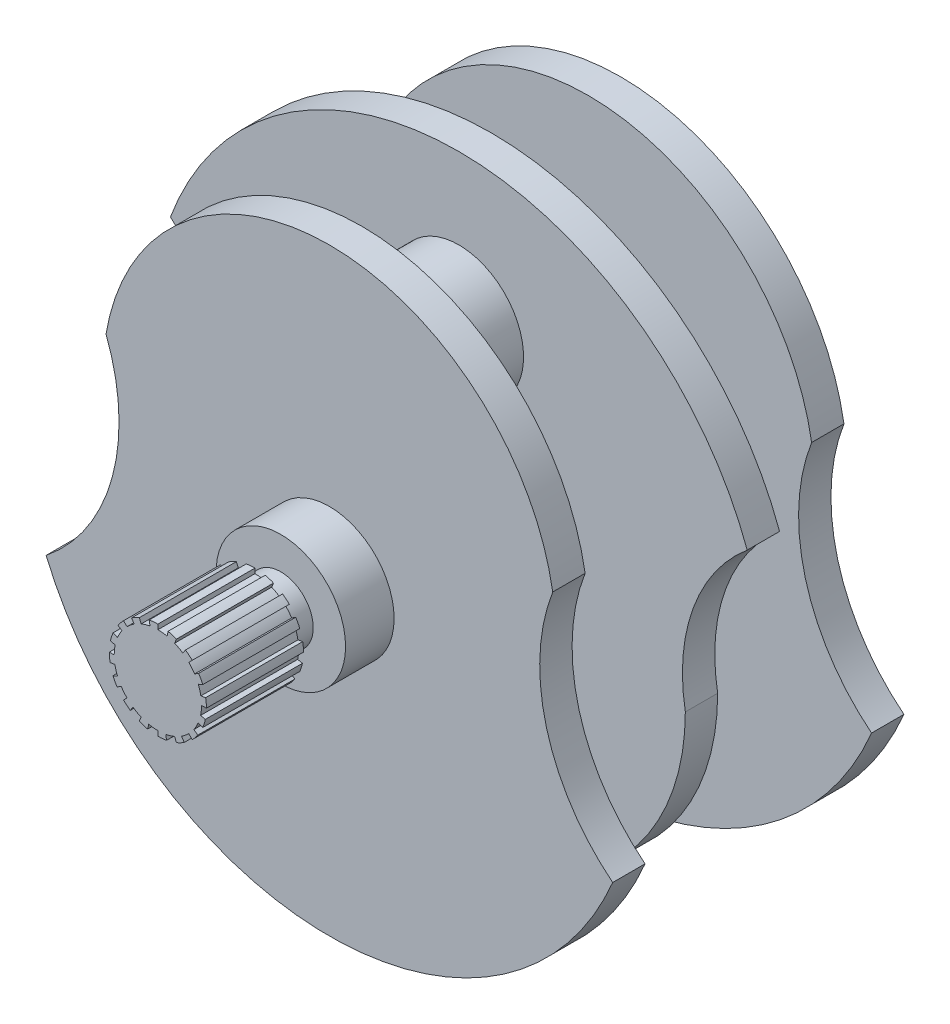
SolidWorks part; units mm, degrees
ref_plane "Front Plane" through (0, 0, 0) normal (0, 0, 1) x (1, 0, 0)
ref_plane "Top Plane" through (0, 0, 0) normal (0, 1, 0) x (1, 0, 0)
ref_plane "Right Plane" through (0, 0, 0) normal (1, 0, 0) x (0, 0, -1)
sketch "Sketch1" plane through (0, 0, 0) normal (0, 0, 1) x (1, 0, 0)
  circle A0 centre (0, 0) radius 20
  dimension "D1" = 20
extrude "Boss-Extrude1" add sketch "Sketch1" along normal blind 15
sketch "Sketch2" plane through (0, 0, 15) normal (0, 0, 1) x (1, 0, 0)
  circle A0 centre (0, 0) radius 10
  dimension "D1" = 10
extrude "Boss-Extrude2" add sketch "Sketch2" along normal blind 8
sketch "Sketch3" plane through (0, 0, 23) normal (0, 0, 1) x (1, 0, 0)
  circle A0 centre (0, 0) radius 15
  dimension "D1" = 15
extrude "Boss-Extrude3" add sketch "Sketch3" along normal blind 30
sketch "Sketch5" plane through (0, 0, 53) normal (0, 0, 1) x (1, 0, 0)
  line L0 (0, 15) -> (0, 13.5)
  line L1 (2.8421, 13.1974) -> (3.1579, 14.6638)
  circle A0 centre (0, 0) radius 15 construction
  arc A1 (0, 13.5) -> (2.8421, 13.1974) centre (0, 0) cw
  arc A2 (3.1579, 14.6638) -> (0, 15) centre (0, 0) ccw
  circle A3 centre (0, 0) radius 15
  point P8 (0, 14.25)
  circle M6 centre (0, 0) radius 15
  dimension "D1" = 13.5
  dimension "D2" = 3
extrude "Cut-Extrude1" cut sketch "Sketch5" against normal up to next contours L0 A1 L1 M6 region at (1.507, 14.1564, 53)
pattern_circular "CirPattern1" count 16 over 360 about axis through (0, 0, 53) along (0, 0, 1) of "Cut-Extrude1"
sketch "Sketch8" plane through (0, 0, 0) normal (0, 0, -1) x (-1, 0, 0)
  arc A0 (69.0293, 31.6168) -> (-69.0293, 31.6168) centre (0, 20) ccw
  arc A5 (-87.5502, -36.8776) -> (87.5502, -36.8776) centre (0, 0) ccw
  arc A6 (-69.0293, 31.6168) -> (-87.5502, -36.8776) centre (-125, 10) cw
  arc A7 (69.0293, 31.6168) -> (87.5502, -36.8776) centre (125, 10) ccw
  dimension "D1" = 70
  dimension "D2" = 95
  dimension "D4" = 60
  dimension "D3" = 20
  dimension "D5" = 10
  dimension "D6" = 125
extrude "Boss-Extrude5" add sketch "Sketch8" along normal blind 10
sketch "Sketch9" plane through (0, 0, -10) normal (0, 0, -1) x (-1, 0, 0)
  circle A0 centre (0, 50) radius 20
  dimension "D2" = 20
  dimension "D1" = 50
extrude "Boss-Extrude6" add sketch "Sketch9" along normal blind 30
sketch "Sketch10" plane through (0, 0, -40) normal (0, 0, -1) x (-1, 0, 0)
  arc A0 (-70, -20) -> (70, -20) centre (0, -20) ccw
  arc A1 (-70, -20) -> (-89.1301, 32.876) centre (-125, -10) ccw
  arc A2 (70, -20) -> (89.1301, 32.876) centre (125, -10) cw
  arc A3 (-89.1301, 32.876) -> (89.1301, 32.876) centre (0, 0) cw
  dimension "D1" = 70
  dimension "D3" = 95
  dimension "D2" = 20
  dimension "D4" = 125
  dimension "D5" = 10
extrude "Boss-Extrude7" add sketch "Sketch10" along normal blind 10
ref_plane "Plane3" through (0, 0, -80) normal (0, 0, -1) x (-1, 0, 0)
sketch "Sketch12" plane through (0, 0, -80) normal (0, 0, -1) x (-1, 0, 0)
  arc A4 (69.0293, 31.6168) -> (-69.0293, 31.6168) centre (0, 20) ccw
  arc A5 (-87.5502, -36.8776) -> (-69.0293, 31.6168) centre (-125, 10) ccw
  arc A6 (-87.5502, -36.8776) -> (87.5502, -36.8776) centre (0, 0) ccw
  arc A7 (69.0293, 31.6168) -> (87.5502, -36.8776) centre (125, 10) ccw
  arc A8 (69.0293, 31.6168) -> (-69.0293, 31.6168) centre (0, 20) ccw
  arc A9 (-87.5502, -36.8776) -> (-69.0293, 31.6168) centre (-125, 10) ccw
  arc A10 (-87.5502, -36.8776) -> (87.5502, -36.8776) centre (0, 0) ccw
  arc A11 (69.0293, 31.6168) -> (87.5502, -36.8776) centre (125, 10) ccw
  dimension "D1" = 0
extrude "Boss-Extrude8" add sketch "Sketch12" along normal blind 10 separate body
sketch "Sketch14" plane through (0, 0, -50) normal (0, 0, -1) x (-1, 0, 0)
  circle A0 centre (0, -50) radius 20
  dimension "D2" = 20
  dimension "D1" = 50
extrude "Boss-Extrude9" add sketch "Sketch14" along normal up to next
sketch "Sketch15" plane through (0, 0, -90) normal (0, 0, -1) x (-1, 0, 0)
  circle A1 centre (0, 0) radius 20
  circle A2 centre (0, 0) radius 20
  dimension "D1" = 0
extrude "Boss-Extrude10" add sketch "Sketch15" along normal blind 15
sketch "Sketch16" plane through (0, 0, -105) normal (0, 0, -1) x (-1, 0, 0)
  circle A1 centre (0, 0) radius 10
  circle A2 centre (0, 0) radius 10
  dimension "D1" = 0
extrude "Boss-Extrude11" add sketch "Sketch16" along normal blind 8
